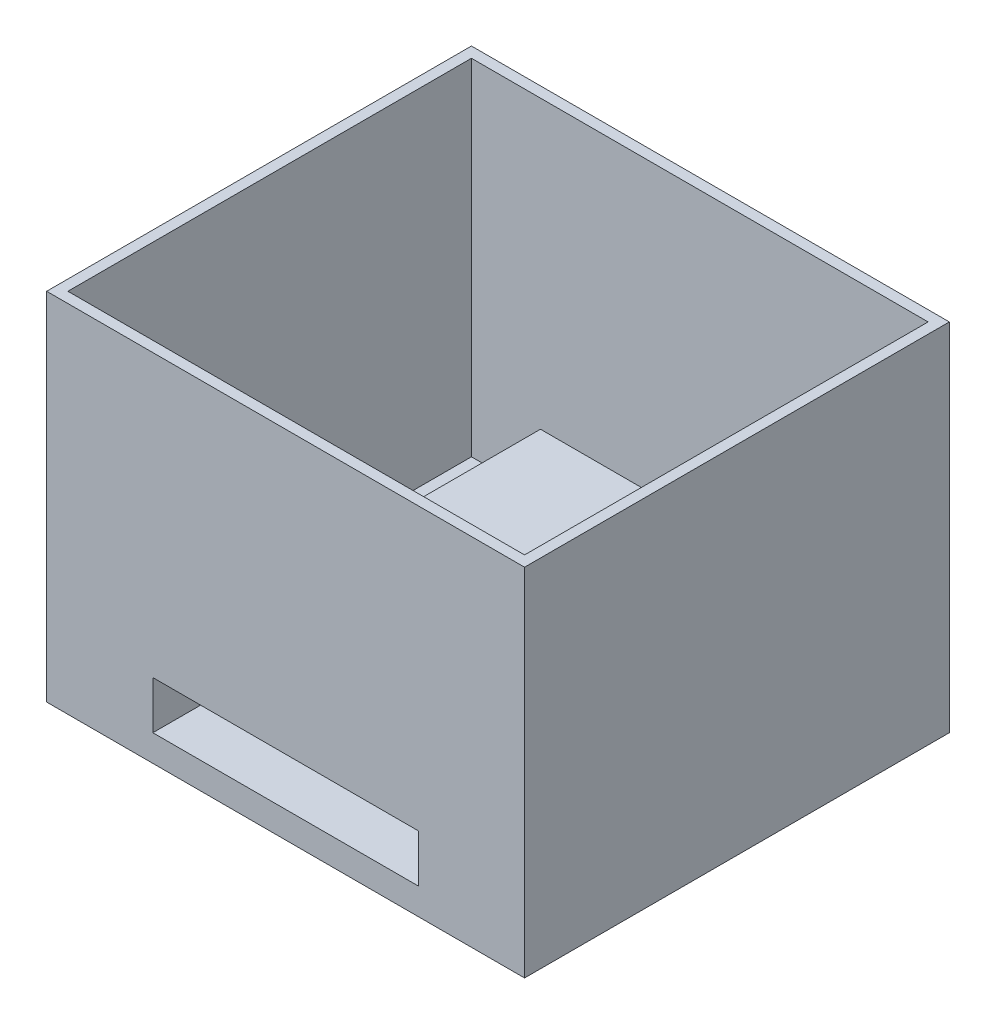
SolidWorks part; units mm, degrees
ref_plane "Front Plane" through (0, 0, 0) normal (0, 0, 1) x (1, 0, 0)
ref_plane "Top Plane" through (0, 0, 0) normal (0, 1, 0) x (1, 0, 0)
ref_plane "Right Plane" through (0, 0, 0) normal (1, 0, 0) x (0, 0, -1)
sketch "Sketch1" plane through (0, 0, 58.5856) normal (0, 0, 1) x (1, 0, 0)
  line L0 (-3.787, 73.767) -> (-3.787, -6.233) construction
  line L1 (-8.787, 44.767) -> (81.213, 44.767)
  line L2 (-8.787, 44.767) -> (-8.787, -22.233)
  line L3 (-8.787, -22.233) -> (81.213, -22.233)
  line L4 (81.213, 44.767) -> (81.213, -22.233)
  line L5 (-3.787, -6.233) -> (76.213, -6.233) construction
  dimension "D1" = 90
  dimension "D2" = 5
  dimension "D3" = 67
  dimension "D4" = 16
extrude "Boss-Extrude1" add sketch "Sketch1" along normal mid plane 80
shell "Shell1" thickness 2
sketch "Sketch2" plane through (0, 0, 98.5856) normal (0, 0, 1) x (1, 0, 0)
  line L0 (81.213, -22.233) -> (81.213, 44.767) construction
  line L1 (11.213, -6.233) -> (61.213, -6.233)
  line L2 (11.213, -6.233) -> (11.213, -19.233)
  line L3 (11.213, -19.233) -> (61.213, -19.233)
  line L4 (61.213, -6.233) -> (61.213, -19.233)
  line L5 (-8.787, -22.233) -> (81.213, -22.233) construction
  point P4 (61.213, -12.733)
  dimension "D1" = 13
  dimension "D2" = 50
  dimension "D3" = 20
  dimension "D4" = 3
extrude "Cut-Extrude4" cut sketch "Sketch2" against normal blind 40
sketch "Sketch4" plane through (0, 0, 98.5856) normal (0, 0, 1) x (1, 0, 0)
  line L1 (9.213, -6.233) -> (63.213, -6.233)
  line L2 (9.213, -6.233) -> (9.213, -19.233)
  line L3 (9.213, -19.233) -> (63.213, -19.233)
  line L4 (63.213, -6.233) -> (63.213, -19.233)
  line L5 (61.213, -19.233) -> (61.213, -6.233) construction
  dimension "D2" = 2
extrude "Boss-Extrude2" add sketch "Sketch4" against normal blind 75
shell "Shell2" thickness 2
